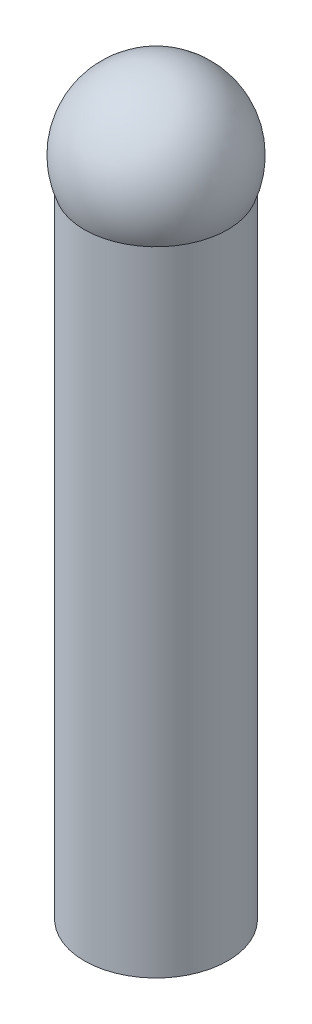
SolidWorks part; units mm, degrees
ref_plane "Спереди" through (0, 0, 0) normal (0, 0, 1) x (1, 0, 0)
ref_plane "Сверху" through (0, 0, 0) normal (0, 1, 0) x (1, 0, 0)
ref_plane "Справа" through (0, 0, 0) normal (1, 0, 0) x (0, 0, -1)
sketch "Эскиз1" plane through (0, 0, 0) normal (0, 1, 0) x (1, 0, 0)
  circle A0 centre (0, 0) radius 0.65
extrude "Бобышка-Вытянуть1" add sketch "Эскиз1" along normal blind 6
sketch "Эскиз3" plane through (0, 0, 0) normal (0, 0, 1) x (1, 0, 0)
  line L0 (0, 0) -> (0, 6) construction
  line L1 (0.7, 6) -> (0.65, 6) construction
  line L2 (0.65, 6) -> (0.65, 6.2598) construction
  line L3 (0.65, 0) -> (0.65, 6) construction
  line L4 (0.65, 6.2598) -> (-0.65, 6.2598) construction
  line L5 (-0.65, 6.2598) -> (-0.65, 6) construction
  line L6 (-0.65, 6) -> (-0.7, 6) construction
  line L7 (0.7, 6) -> (-0.7, 6)
  circle A0 centre (0, 6) radius 0.7
  dimension "D2" = 1.4
  dimension "D1" = 6
revolve "Повернуть23" add sketch "Эскиз3" angle 360 about L7 region at (0, 6.2971, 0)
